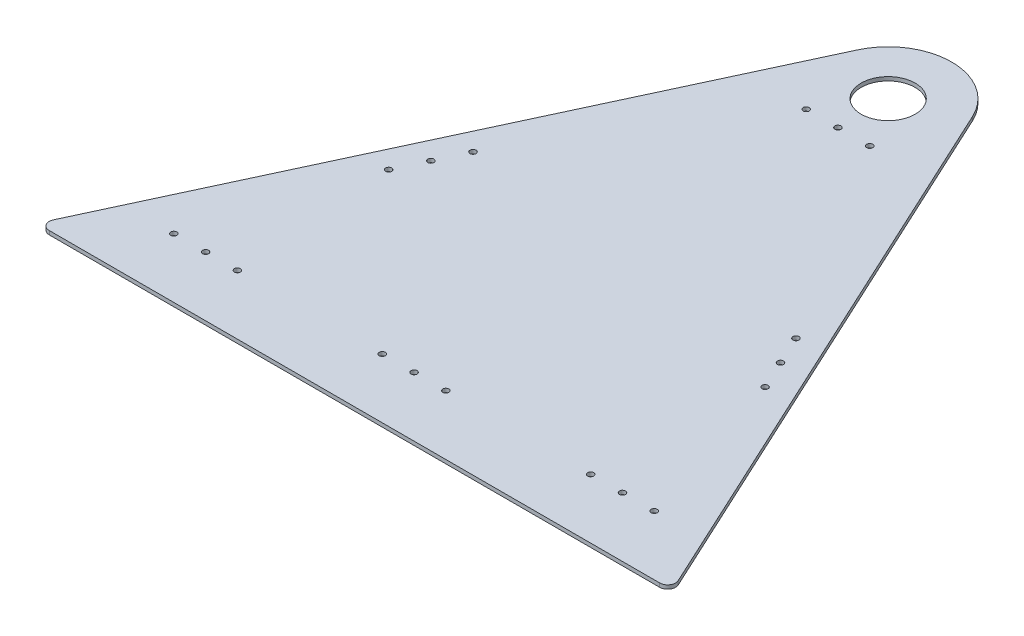
SolidWorks part; units mm, degrees
ref_plane "Front Plane" through (0, 0, 0) normal (0, 0, 1) x (1, 0, 0)
ref_plane "Top Plane" through (0, 0, 0) normal (0, 1, 0) x (1, 0, 0)
ref_plane "Right Plane" through (0, 0, 0) normal (1, 0, 0) x (0, 0, -1)
sketch "Sketch1" plane through (0, 0, 0) normal (0, 1, 0) x (1, 0, 0)
  line L0 (254, 0) -> (254, 477.52) construction
  line L1 (9.9467, 0) -> (498.0533, 0)
  line L2 (0, 0) -> (0, 477.52) construction
  line L3 (0, 477.52) -> (508, 477.52) construction
  line L4 (508, 0) -> (508, 477.52) construction
  line L5 (4.1865, 9.0227) -> (207.9189, 448.1016)
  line L6 (300.0811, 448.1016) -> (503.8135, 9.0227)
  line L7 (503.8135, 9.0227) -> (508, 0) construction
  line L8 (508, 0) -> (498.0533, 0) construction
  line L9 (9.9467, 0) -> (0, 0) construction
  line L10 (0, 0) -> (4.1865, 9.0227) construction
  circle A0 centre (254, 426.72) radius 21.59
  arc A1 (207.9189, 448.1016) -> (300.0811, 448.1016) centre (254, 426.72) cw
  arc A2 (498.0533, 0) -> (503.8135, 9.0227) centre (498.0533, 6.35) ccw
  arc A3 (9.9467, 0) -> (4.1865, 9.0227) centre (9.9467, 6.35) cw
  point P9 (3.5967, 0)
  point P12 (3.5967, 6.35)
  point P19 (4.5944, 2.9331)
  point P20 (254, 477.52)
  point P21 (504.4033, 0)
  point P22 (504.4033, 6.35)
  dimension "D4" = 43.18
  dimension "D5" = 6.35
  dimension "D7" = 50.8
  dimension "D1" = 508
  dimension "D2" = 477.52
  dimension "D3" = 426.72
  dimension "D6" = 65.109
  dimension "D8" = 244.0533
  dimension "D9" = 484.0425
  dimension "D10" = 244.0533
base flange "Base-Flange1" sketch "Sketch1" thickness 3.0378 reverse thickness direction no parameters "D1"=3.175
hole_wizard "#11 (0.191) Diameter Hole1" positions "Sketch6" profile "Sketch7" hole size "#11" standard "ANSI Inch" end condition through all
sketch "Sketch6" plane through (0, 0, 0) normal (0, 1, 0) x (1, 0, 0)
  line L0 (254, 0) -> (254, 477.52) construction
  line L1 (9.9467, 0) -> (498.0533, 0) construction
  line L2 (61.9479, 47.625) -> (112.7479, 47.625) construction
  line L4 (103.4999, 177.8) -> (124.8815, 223.8811) construction
  line L5 (207.9189, 448.1016) -> (4.1865, 9.0227) construction
  line L6 (401.9473, 228.5622) -> (382.4379, 195.5143) construction
  line L7 (503.8135, 9.0227) -> (300.0811, 448.1016) construction
  arc A0 (300.0811, 448.1016) -> (207.9189, 448.1016) centre (254, 426.72) ccw construction
  point P0 (61.9479, 47.625)
  point P2 (87.3479, 47.625)
  point P4 (112.7479, 47.625)
  point P6 (228.6, 47.625)
  point P8 (254, 47.625)
  point P26 (446.0521, 47.625)
  point P27 (420.6521, 47.625)
  point P28 (395.2521, 47.625)
  point P29 (279.4, 47.625)
  point P30 (103.4999, 177.8)
  point P32 (114.1907, 200.8405)
  point P34 (124.8815, 223.8811)
  point P43 (404.5001, 177.8)
  point P44 (393.8093, 200.8405)
  point P45 (383.1185, 223.8811)
  dimension "D1" = 50.8
  dimension "D2" = 25.4
  dimension "D3" = 25.4
  dimension "D4" = 47.625
  dimension "D5" = 50.8
  dimension "D6" = 19.05
  dimension "D7" = 177.8
  dimension "D8" = 141.2521
  dimension "D9" = 25.4
  dimension "D10" = 166.6521
  dimension "D11" = 47.625
sketch "Sketch7" plane through (61.9479, 0, -47.625) normal (1, 0, 0) x (0, 0, 1)
  line L0 (0, 0) -> (0, 3.0378)
  line L1 (0, 3.0378) -> (2.4257, 3.0378)
  line L2 (2.4257, 3.0378) -> (2.4257, 0)
  line L5 (2.4257, 0) -> (0, 0)
  line L11 (0, -6.35) -> (0, 107.95) construction
  dimension "Thru Hole Dia." = 4.8514
  dimension "Thru Hole Depth" = 3.0378
hole_wizard "#11 (0.191) Diameter Hole2" positions "Sketch8" profile "Sketch9" hole size "#11" standard "ANSI Inch" end condition through all
sketch "Sketch8" plane through (0, 0, 0) normal (0, 1, 0) x (1, 0, 0)
  line L0 (254, 477.52) -> (254, 386.588) construction
  circle A0 centre (254, 426.72) radius 21.59 construction
  arc A1 (300.0811, 448.1016) -> (207.9189, 448.1016) centre (254, 426.72) ccw construction
  point P0 (228.6, 386.588)
  point P2 (254, 386.588)
  point P7 (279.4, 386.588)
  dimension "D1" = 25.4
  dimension "D2" = 25.4
  dimension "D3" = 40.132
sketch "Sketch9" plane through (228.6, 0, -386.588) normal (1, 0, 0) x (0, 0, 1)
  line L0 (0, 0) -> (0, 3.0378)
  line L1 (0, 3.0378) -> (2.4257, 3.0378)
  line L2 (2.4257, 3.0378) -> (2.4257, 0)
  line L5 (2.4257, 0) -> (0, 0)
  line L11 (0, -6.35) -> (0, 107.95) construction
  dimension "Thru Hole Dia." = 4.8514
  dimension "Thru Hole Depth" = 3.0378
sketch "Bend-Lines1" [suppressed] plane through (0, 0, 0) normal (0, 1, 0) x (1, 0, 0)
sketch "Bounding-Box1" [suppressed] plane through (0, 0, 0) normal (0, 1, 0) x (1, 0, 0)
sheet metal parameters "Sheet-Metal1" thickness 3.0378 parameters "D1"=3.175
flat pattern "Flat-Pattern1" [suppressed]
sketch "Bend-Lines2" plane through (0, 0, 0) normal (0, 1, 0) x (1, 0, 0)
sketch3d "Bounding-Box2" [suppressed]
  line L0 (199.3882, 50.8, 0) -> (-199.3882, 50.8, 0) construction
  line L1 (199.3882, -304.8, 0) -> (-199.3882, -304.8, 0) construction
  line L2 (199.3882, 50.8, 0) -> (199.3882, -304.8, 0) construction
  line L3 (-199.3882, 50.8, 0) -> (-199.3882, -304.8, 0) construction
sheet metal parameters "Sheet-Metal2" thickness 3.0378 parameters "D1"=3.175
flat pattern "Flat-Pattern1"
sketch "Bend-Lines2" plane through (0, 0, 0) normal (0, 1, 0) x (1, 0, 0)
sketch3d "Bounding-Box2" [suppressed]
  line L0 (250.0188, 50.8, 0) -> (-250.0188, 50.8, 0) construction
  line L1 (250.0188, -393.7, 0) -> (-250.0188, -393.7, 0) construction
  line L2 (250.0188, 50.8, 0) -> (250.0188, -393.7, 0) construction
  line L3 (-250.0188, 50.8, 0) -> (-250.0188, -393.7, 0) construction
sheet metal parameters "Sheet-Metal3" thickness 3.0378 parameters "D1"=3.175
flat pattern "Flat-Pattern1"
sketch "Bend-Lines2" plane through (0, 0, 0) normal (0, 1, 0) x (1, 0, 0)
sketch3d "Bounding-Box2" [suppressed]
  line L0 (250.4033, 50.8, 0) -> (-250.4032, 50.8, 0) construction
  line L1 (250.4033, -426.72, 0) -> (-250.4032, -426.72, 0) construction
  line L2 (250.4033, 50.8, 0) -> (250.4033, -426.72, 0) construction
  line L3 (-250.4032, 50.8, 0) -> (-250.4032, -426.72, 0) construction
equation "\"D3@Sketch1\"=\"D2@Sketch1\"-2"
